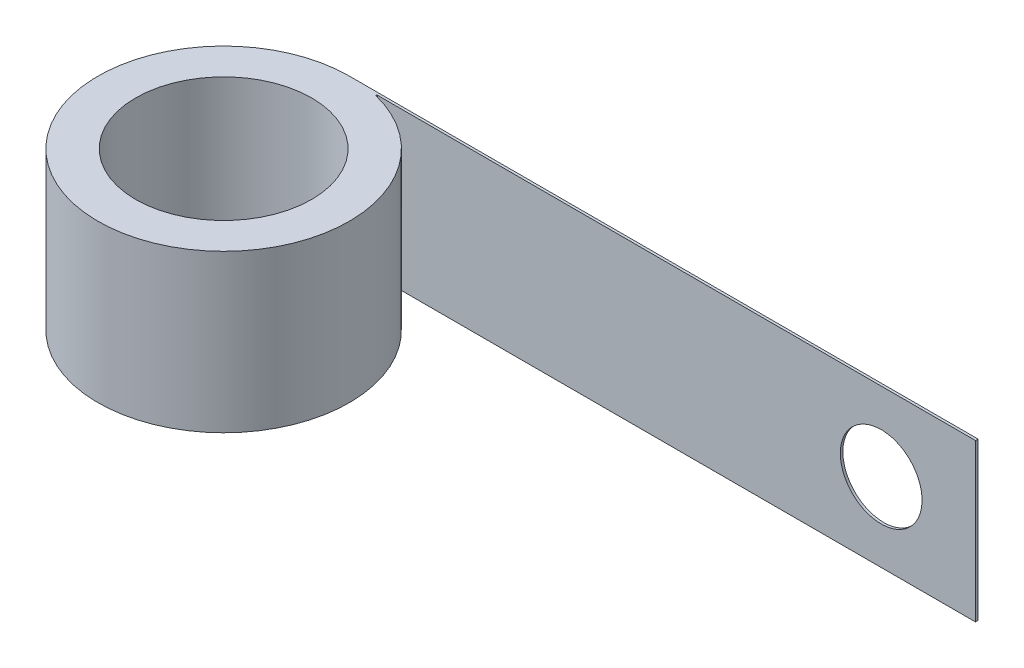
SolidWorks part; units mm, degrees
ref_plane "Front Plane" through (0, 0, 0) normal (0, 0, 1) x (1, 0, 0)
ref_plane "Top Plane" through (0, 0, 0) normal (0, 1, 0) x (1, 0, 0)
ref_plane "Right Plane" through (0, 0, 0) normal (1, 0, 0) x (0, 0, -1)
sketch "Sketch1" plane through (0, 0, 0) normal (0, 1, 0) x (1, 0, 0)
  line L0 (0, 5.08) -> (25.4, 5.08)
  line L1 (25.4, 4.9784) -> (1.0109, 4.9784)
  line L2 (25.4, 4.9784) -> (25.4, 5.08)
  circle A0 centre (0, 0) radius 3.556
  arc A1 (0, 5.08) -> (1.0109, 4.9784) centre (0, 0) ccw
  dimension "D1" = 7.112
  dimension "D2" = 10.16
  dimension "D3" = 0.1016
  dimension "D4" = 25.4
extrude "Boss-Extrude1" add sketch "Sketch1" along normal blind 6.35
sketch "Sketch2" plane through (0, 0, -5.08) normal (0, 0, -1) x (-1, 0, 0)
  line L0 (-25.4, 6.35) -> (-25.4, 0) construction
  circle A0 centre (-21.59, 3.175) radius 1.651
  point P4 (-25.4, 3.175)
  dimension "D1" = 3.302
  dimension "D2" = 3.81
extrude "Cut-Extrude1" cut sketch "Sketch2" against normal blind 6.35
fillet "Fillet1" radius 0.0254 1 edges at (1.0109, 3.175, -4.9784)
